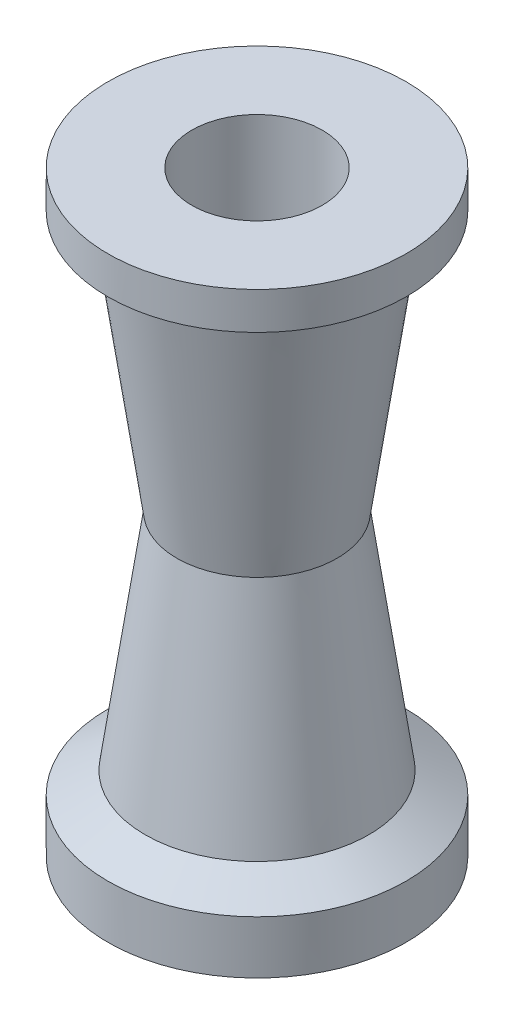
SolidWorks part; units mm, degrees
ref_plane "Front Plane" through (0, 0, 0) normal (0, 0, 1) x (1, 0, 0)
ref_plane "Top Plane" through (0, 0, 0) normal (0, 1, 0) x (1, 0, 0)
ref_plane "Right Plane" through (0, 0, 0) normal (1, 0, 0) x (0, 0, -1)
sketch "Sketch2" plane through (0, 0, 0) normal (0, 0, 1) x (1, 0, 0)
  line L0 (1.75, 8) -> (1.75, -8)
  line L1 (1.75, -8) -> (4, -8)
  line L7 (4, 8) -> (1.75, 8)
  line L8 (0, 0) -> (0, 4.4875) construction
  line L9 (4, 8) -> (4, 6)
  line L10 (4, 6) -> (3, 6)
  line L11 (3, 6) -> (2.15, 0)
  line L12 (4, -8) -> (4, -6)
  line L13 (4, -6) -> (3, -6)
  line L14 (3, -6) -> (2.15, 0)
  point P3 (1.75, 0)
  dimension "D1" = 2
  dimension "D2" = 0.4
  dimension "D3" = 1.75
  dimension "D4" = 4
  dimension "D5" = 16
  dimension "D6" = 1
revolve "Revolve1" add sketch "Sketch2" angle 360 about L8
chamfer "Chamfer1" distance 1 angle 60 1 edges at (0, 6, -4) first distance on face at (0, 8, -4)
chamfer "Chamfer2" distance 1 angle 30 1 edges at (0, -6, -4) first distance on face at (0, -6, -3)
